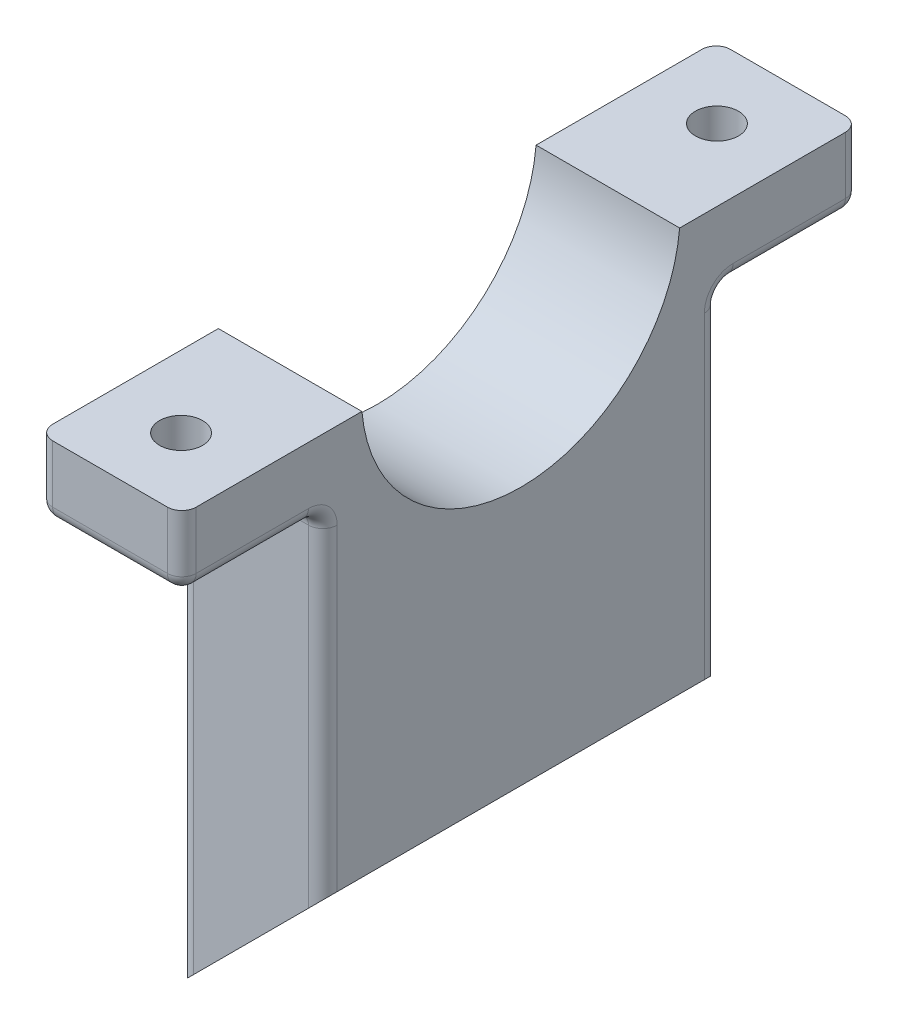
SolidWorks part; units mm, degrees
ref_plane "Front Plane" through (0, 0, 0) normal (0, 0, 1) x (1, 0, 0)
ref_plane "Top Plane" through (0, 0, 0) normal (0, 1, 0) x (1, 0, 0)
ref_plane "Right Plane" through (0, 0, 0) normal (1, 0, 0) x (0, 0, -1)
sketch "Sketch4" plane through (0, 0, 0) normal (1, 0, 0) x (0, 0, -1)
  line L2 (-23.6125, -1) -> (-23.6125, -6)
  line L3 (-23.6125, -6) -> (-13.7899, -6)
  line L4 (23.6125, -1) -> (23.6125, -6)
  line L5 (13.7899, -6) -> (23.6125, -6)
  line L7 (-23.6125, -1) -> (-11.0674, -1)
  line L8 (11.0674, -1) -> (23.6125, -1)
  line L10 (-13.7899, -6) -> (-13.7899, -39.1125)
  line L11 (13.7899, -6) -> (13.7899, -39.1125)
  line L12 (-13.7899, -39.1125) -> (13.7899, -39.1125)
  arc A0 (-11.0674, -1) -> (11.0674, -1) centre (0, 0) ccw
  point P3 (0, -11.1125)
  dimension "D2" = 22.225
  dimension "D1" = 5
  dimension "D3" = 22.1348
  dimension "D4" = 28
  dimension "D5" = 12.5451
  dimension "D6" = 12.5451
  dimension "D7" = 9.8226
  dimension "D8" = 9.8226
  dimension "D9" = 27.5799
extrude "Clamp Extrude" add sketch "Sketch4" along normal blind 10
sketch "Hole" plane through (0, -6, 0) normal (0, -1, 0) x (1, 0, 0)
  line L0 (0, 0) -> (10, 0)
  line L4 (0, 23.6125) -> (0, 13.7899) construction
  line L5 (10, 23.6125) -> (10, 13.7899) construction
  line L9 (8.3198, 18.6649) -> (6.6599, 21.5399)
  line L10 (10, 23.6125) -> (0, 23.6125) construction
  line L11 (10, 13.7899) -> (0, 13.7899) construction
  line L12 (6.6599, 21.5399) -> (3.3401, 21.5399)
  line L13 (3.3401, 21.5399) -> (1.6802, 18.6649)
  line L14 (1.6802, 18.6649) -> (3.3401, 15.7899)
  line L15 (3.3401, 15.7899) -> (6.6599, 15.7899)
  line L16 (6.6599, 15.7899) -> (8.3198, 18.6649)
  line L17 (10, 13.7899) -> (10, -13.7899) construction
  line L18 (6.6599, -15.7899) -> (8.3198, -18.6649)
  line L19 (3.3401, -15.7899) -> (6.6599, -15.7899)
  line L20 (1.6802, -18.6649) -> (3.3401, -15.7899)
  line L21 (3.3401, -21.5399) -> (1.6802, -18.6649)
  line L22 (6.6599, -21.5399) -> (3.3401, -21.5399)
  line L23 (8.3198, -18.6649) -> (6.6599, -21.5399)
  circle A0 centre (5, 18.6649) radius 1.5
  circle A3 centre (5, 18.6649) radius 2.875 construction
  circle A4 centre (5, -18.6649) radius 1.5
  dimension "D1" = 3
  dimension "D6" = 5.75
  dimension "D4" = 10
  dimension "D5" = 5
  dimension "D2" = 9.8226
  dimension "D3" = 4.875
sketch "Sketch10" plane through (0, 0, -13.7899) normal (0, 0, -1) x (-1, 0, 0)
  line L0 (0, -39.1125) -> (-10, -29.1125)
  line L1 (-10, -39.1125) -> (-10, -6) construction
  line L2 (-10, -29.1125) -> (-10, -39.1125)
  line L3 (-10, -39.1125) -> (0, -39.1125)
  dimension "D1" = 45
extrude "Cut-Extrude3" cut sketch "Sketch10" against normal through all
fillet "Fillet2" radius 1 12 edges at (10, -17.5562, 13.7899) (0, -6, 18.7012) (0, -6, -18.7012) (10, -6, 18.7012) (5, -6, 23.6125) (5, -6, 13.7899) (5, -6, -23.6125) (5, -6, -13.7899) (10, -6, -18.7012) (0, -22.5562, 13.7899) (0, -22.5562, -13.7899) (10, -17.5562, -13.7899)
fillet "Fillet3" radius 1 8 edges at (0.2929, -5.7071, -23.3196) (9.7071, -5.7071, -23.3196) (9.7071, -5.7071, 23.3196) (0.2929, -5.7071, 23.3196) (0, -3, -23.6125) (10, -3, -23.6125) (10, -3, 23.6125) (0, -3, 23.6125)
extrude "Cut-Extrude4" cut sketch "Hole" against normal blind 2.2 contours L14 L15 L16 L9 L12 L13 | L21 L20 L19 L18 L23 L22
extrude "Cut-Extrude5" cut sketch "Hole<5>" against normal through all contours A0 | A4
sketch "Hole<5>" plane through (0, -6, 0) normal (0, -1, 0) x (1, 0, 0) same geometry as "Hole"
equation "\"D5@Hole\"=\"D4@Hole\"/2"
equation "\"D3@Hole\"=\"D6@Hole\"/2+2"
equation "\"D6@Sketch4\"=\"D5@Sketch4\""
equation "\"D8@Sketch4\"=\"D7@Sketch4\""
